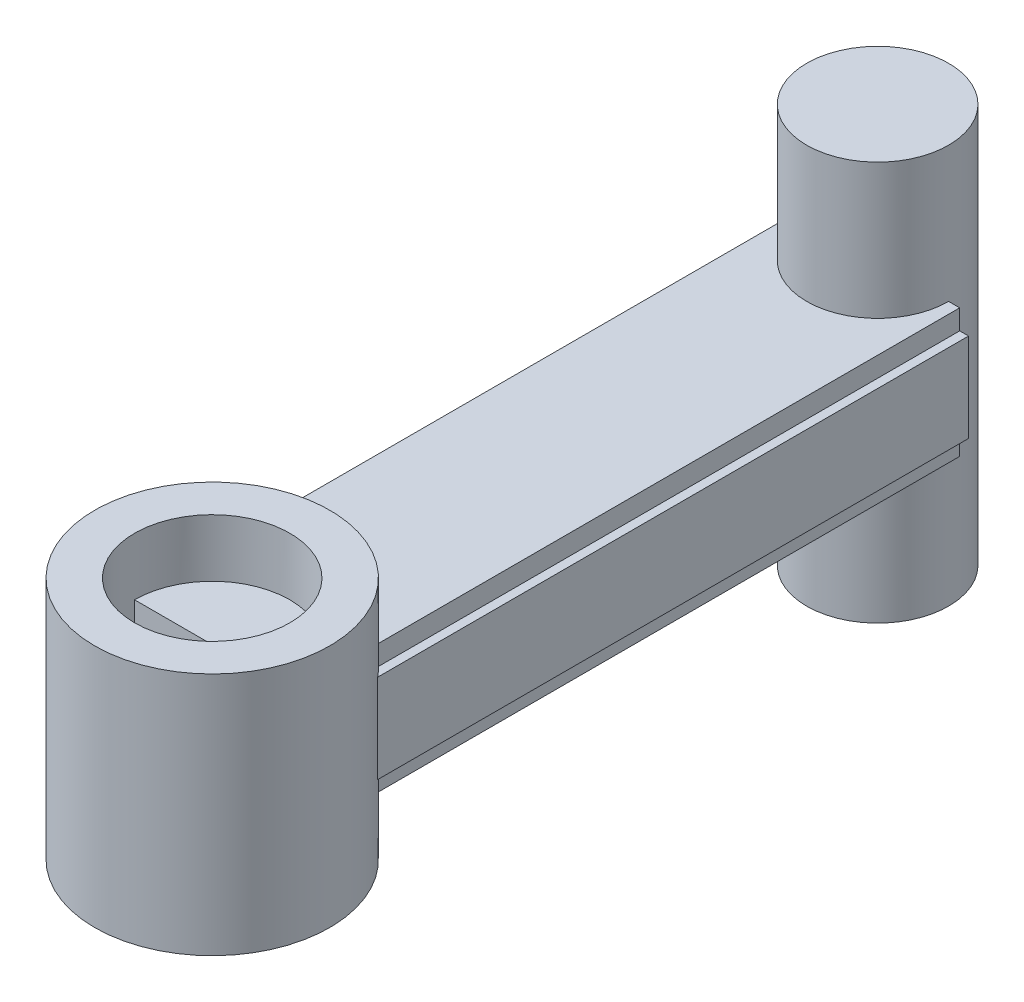
SolidWorks part; units mm, degrees
ref_plane "前视基准面" through (0, 0, 0) normal (0, 0, 1) x (1, 0, 0)
ref_plane "上视基准面" through (0, 0, 0) normal (0, 1, 0) x (1, 0, 0)
ref_plane "右视基准面" through (0, 0, 0) normal (1, 0, 0) x (0, 0, -1)
other "Configuration Table"
sketch "草图1" plane through (0, 0, 0) normal (0, 1, 0) x (1, 0, 0)
  circle A0 centre (0, 0) radius 32
extrude "凸台-拉伸1" add sketch "草图1" along normal blind 90 and the other way blind 90
sketch "草图2" plane through (0, 0, 0) normal (0, 0, 1) x (1, 0, 0)
  line L1 (-37, -29) -> (37, -29)
  line L2 (-37, -29) -> (-37, 29)
  line L3 (-37, 29) -> (37, 29)
  line L4 (37, -29) -> (37, 29)
  line L5 (-37, -29) -> (37, 29) construction
  line L6 (-37, 29) -> (37, -29) construction
  point P0 (0, 0)
extrude "凸台-拉伸2" add sketch "草图2" along normal blind 300
sketch "草图3" plane through (0, 0, 0) normal (0, 0, 1) x (1, 0, 0)
  line L0 (-37, 29) -> (-37, -29) construction
  line L1 (37, -20) -> (41, -20)
  line L2 (37, -20) -> (37, 20)
  line L3 (37, 20) -> (41, 20)
  line L4 (41, -20) -> (41, 20)
  line L5 (37, -20) -> (41, 20) construction
  line L6 (37, 20) -> (41, -20) construction
  line L7 (-41, -20) -> (-37, -20)
  line L8 (-41, -20) -> (-41, 20)
  line L9 (-41, 20) -> (-37, 20)
  line L10 (-37, -20) -> (-37, 20)
  line L11 (-41, -20) -> (-37, 20) construction
  line L12 (-41, 20) -> (-37, -20) construction
  point P0 (39, 0)
  point P5 (-39, 0)
extrude "凸台-拉伸3" add sketch "草图3" along normal blind 300
sketch "草图4" plane through (0, 0, 0) normal (0, 1, 0) x (1, 0, 0)
  line L0 (37, -300) -> (-37, -300) construction
  circle A0 centre (0, -300) radius 35
  circle A1 centre (0, -300) radius 53
extrude "凸台-拉伸4" add sketch "草图4" along normal blind 55 and the other way blind 55
